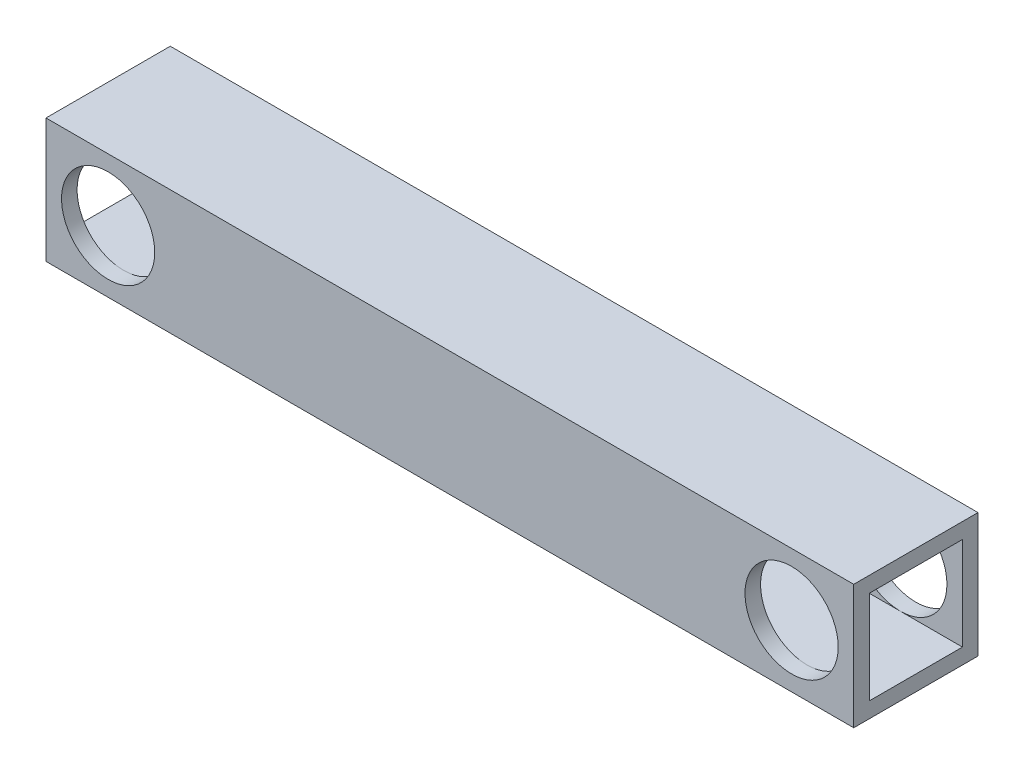
SolidWorks part; units mm, degrees
ref_plane "Front Plane" through (0, 0, 0) normal (0, 0, 1) x (1, 0, 0)
ref_plane "Top Plane" through (0, 0, 0) normal (0, 1, 0) x (1, 0, 0)
ref_plane "Right Plane" through (0, 0, 0) normal (1, 0, 0) x (0, 0, -1)
sketch "Sketch1" plane through (0, 0, 0) normal (0, 0, 1) x (1, 0, 0)
  line L0 (-12.7, 0) -> (0, 0) construction
  line L1 (152.4, 12.7) -> (-12.7, 12.7)
  line L2 (152.4, 12.7) -> (152.4, -12.7)
  line L3 (152.4, -12.7) -> (-12.7, -12.7)
  line L4 (-12.7, 12.7) -> (-12.7, -12.7)
  line L5 (0, 0) -> (0, -12.7) construction
  line L6 (139.7, 0) -> (152.4, 0) construction
  line L7 (139.7, 0) -> (139.7, -12.7) construction
  circle A0 centre (0, 0) radius 9.525
  circle A1 centre (139.7, 0) radius 9.525
  dimension "D2" = 19.05
  dimension "D3" = 139.7
  dimension "D4" = 19.05
  dimension "D1" = 25.4
extrude "Boss-Extrude1" add sketch "Sketch1" along normal blind 25.4
sketch "Sketch2" plane through (152.4, 0, 0) normal (1, 0, 0) x (0, 0, -1)
  line L8 (-3.175, -9.525) -> (-3.175, 9.525)
  line L9 (-3.175, 9.525) -> (-22.225, 9.525)
  line L10 (-22.225, 9.525) -> (-22.225, -9.525)
  line L11 (-22.225, -9.525) -> (-3.175, -9.525)
  line L12 (-3.175, -9.525) -> (-3.175, 9.525)
  line L13 (-3.175, 9.525) -> (-22.225, 9.525)
  line L14 (-22.225, 9.525) -> (-22.225, -9.525)
  line L15 (-22.225, -9.525) -> (-3.175, -9.525)
  dimension "D1" = 3.175
extrude "Cut-Extrude1" cut sketch "Sketch2" against normal through all
